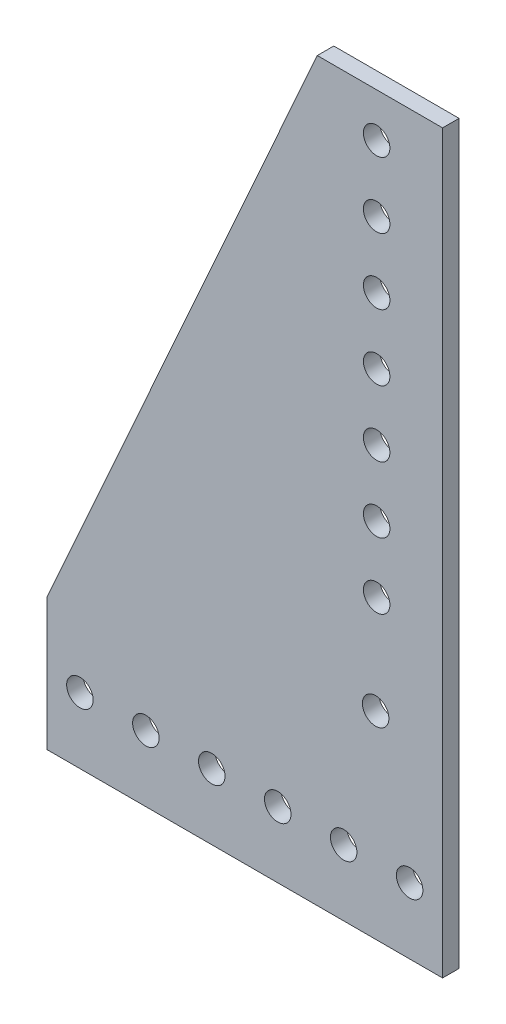
SolidWorks part; units mm, degrees
material "6061-T6 (SS)"
ref_plane "Front Plane" through (0, 0, 0) normal (0, 0, 1) x (1, 0, 0)
ref_plane "Top Plane" through (0, 0, 0) normal (0, 1, 0) x (1, 0, 0)
ref_plane "Right Plane" through (0, 0, 0) normal (1, 0, 0) x (0, 0, -1)
sketch "Sketch1" plane through (0, 0, 0) normal (0, 0, 1) x (1, 0, 0)
  line L1 (-128, 138.6667) -> (49.8, 138.6667)
  line L2 (-128, 138.6667) -> (-128, -115.3333)
  line L3 (-128, -115.3333) -> (49.8, -115.3333)
  line L4 (49.8, 138.6667) -> (49.8, -115.3333)
  dimension "D1" = 254
  dimension "D2" = 177.8
extrude "Boss-Extrude1" add sketch "Sketch1" along normal blind 3.175
sketch "Sketch2" plane through (0, 0, 3.175) normal (0, 0, 1) x (1, 0, 0)
  line L0 (-39.1, -115.3333) -> (-39.1, 138.6667) construction
  line L1 (-128, -115.3333) -> (49.8, -115.3333) construction
  line L2 (49.8, 138.6667) -> (-128, 138.6667) construction
  line L3 (-39.1, -108.9833) -> (-39.1, -96.2833) construction
  circle A0 centre (-39.1, -108.9833) radius 2.5527 construction
  circle A1 centre (-39.1, -96.2833) radius 2.5527 construction
  circle A2 centre (-39.1, -83.5833) radius 2.5527 construction
  circle A3 centre (-39.1, -70.8833) radius 2.5527 construction
  circle A4 centre (-39.1, -58.1833) radius 2.5527
  circle A5 centre (-39.1, -45.4833) radius 2.5527
  circle A6 centre (-39.1, -32.7833) radius 2.5527
  circle A7 centre (-39.1, -20.0833) radius 2.5527
  circle A8 centre (-39.1, -7.3833) radius 2.5527
  circle A9 centre (-39.1, 5.3167) radius 2.5527
  circle A10 centre (-39.1, 18.0167) radius 2.5527
  circle A11 centre (-39.1, 30.7167) radius 2.5527
  circle A12 centre (-39.2905, -77.2333) radius 2.5527
  dimension "D1" = 6.35
  dimension "D2" = 5.1054
  dimension "D5" = 5.1054
  dimension "D6" = 19.05
  dimension "D3" = 12.7
  dimension "D4" = 12
extrude "Cut-Extrude1" cut sketch "Sketch2" against normal through all
sketch "Sketch3" plane through (0, 0, 3.175) normal (0, 0, 1) x (1, 0, 0)
  line L0 (30.75, -102.6333) -> (-17.6342, -102.6333) construction
  line L1 (-128, -115.3333) -> (49.8, -115.3333) construction
  line L2 (49.8, -115.3333) -> (49.8, 138.6667) construction
  line L3 (30.75, -102.6333) -> (18.05, -102.6333) construction
  circle A0 centre (30.75, -102.6333) radius 2.5527
  circle A1 centre (18.05, -102.6333) radius 2.5527
  circle A2 centre (5.35, -102.6333) radius 2.5527
  circle A3 centre (-7.35, -102.6333) radius 2.5527
  circle A4 centre (-20.05, -102.6333) radius 2.5527
  circle A5 centre (-32.75, -102.6333) radius 2.5527
  circle A6 centre (-45.45, -102.6333) radius 2.5527
  circle A7 centre (-58.15, -102.6333) radius 2.5527
  circle A8 centre (-70.85, -102.6333) radius 2.5527
  circle A9 centre (-83.55, -102.6333) radius 2.5527
  circle A10 centre (-96.25, -102.6333) radius 2.5527
  circle A11 centre (-108.95, -102.6333) radius 2.5527
  dimension "D3" = 5.1054
  dimension "D1" = 12.7
  dimension "D2" = 19.05
  dimension "D4" = 12.7
extrude "Cut-Extrude2" cut sketch "Sketch3" against normal through all
sketch "Sketch4" plane through (0, 0, 3.175) normal (0, 0, 1) x (1, 0, 0)
  line L0 (-128, -115.3333) -> (-102.6, -115.3333)
  line L1 (-128, -115.3333) -> (49.8, -115.3333) construction
  line L2 (-102.6, -115.3333) -> (-102.6, -89.9333)
  line L3 (-102.6, -89.9333) -> (-50.53, 26.4641)
  line L4 (-50.53, 26.4641) -> (-26.4, 26.4641)
  line L5 (-26.4, 26.4641) -> (-26.4, -89.9333)
  line L6 (-26.4, -89.9333) -> (-26.4, -115.3333)
  line L7 (-26.4, -115.3333) -> (49.8, -115.3333)
  line L8 (49.8, -115.3333) -> (49.8, 138.6667)
  line L9 (49.8, 138.6667) -> (-128, 138.6667)
  line L10 (-128, 138.6667) -> (-128, -115.3333)
  dimension "D1" = 25.4
  dimension "D2" = 76.2
  dimension "D3" = 24.13
  dimension "D6" = 25.4
  dimension "D7" = 25.4
extrude "Cut-Extrude3" cut sketch "Sketch4" against normal through all
